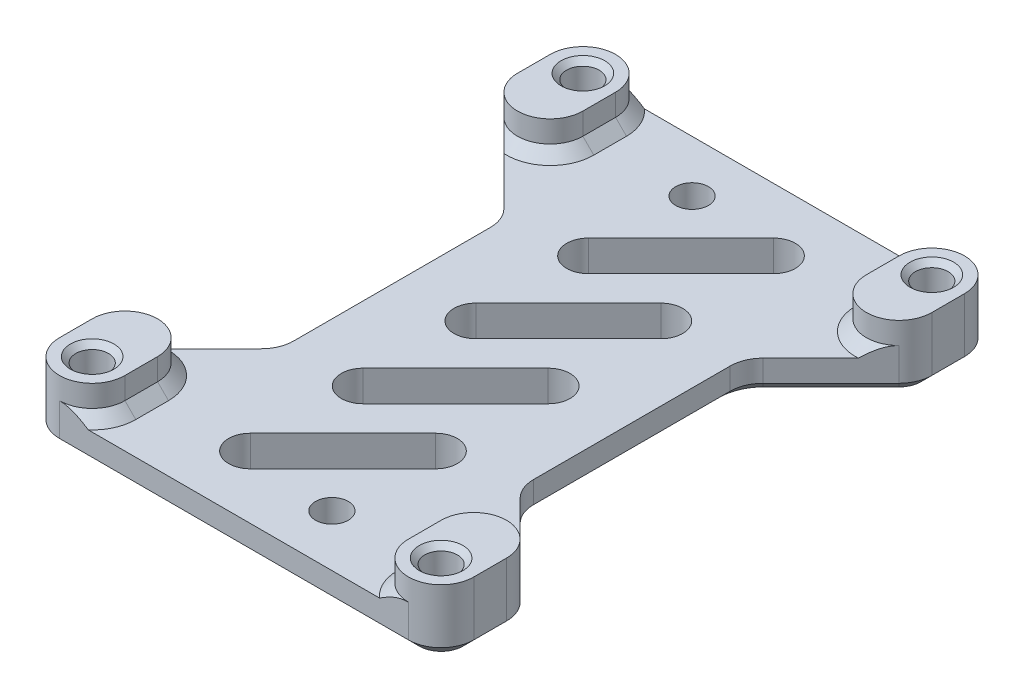
SolidWorks part; units mm, degrees
ref_plane "前视基准面" through (0, 0, 0) normal (0, 0, 1) x (1, 0, 0)
ref_plane "上视基准面" through (0, 0, 0) normal (0, 1, 0) x (1, 0, 0)
ref_plane "右视基准面" through (0, 0, 0) normal (1, 0, 0) x (0, 0, -1)
other "Configuration Table"
sketch "草图1" plane through (0, 0, 0) normal (0, 1, 0) x (1, 0, 0)
  line L1 (-19, -25.5) -> (19, -25.5)
  line L2 (-19, -25.5) -> (-19, 25.5)
  line L3 (-19, 25.5) -> (19, 25.5)
  line L4 (19, -25.5) -> (19, 25.5)
  line L5 (-19, -25.5) -> (19, 25.5) construction
  line L6 (-19, 25.5) -> (19, -25.5) construction
  point P0 (0, 0)
  dimension "D1" = 38
  dimension "D2" = 51
extrude "凸台-拉伸1" add sketch "草图1" along normal blind 6
sketch "草图2" plane through (0, 6, 0) normal (0, 1, 0) x (1, 0, 0)
  line L1 (-16, -22.5) -> (16, -22.5) construction
  line L2 (-16, -22.5) -> (-16, 22.5) construction
  line L3 (-16, 22.5) -> (16, 22.5) construction
  line L4 (16, -22.5) -> (16, 22.5) construction
  line L5 (-16, -22.5) -> (16, 22.5) construction
  line L6 (-16, 22.5) -> (16, -22.5) construction
  circle A0 centre (16, 22.5) radius 1.5
  circle A1 centre (16, -22.5) radius 1.5
  circle A2 centre (-16, 22.5) radius 1.5
  circle A3 centre (-16, -22.5) radius 1.5
  point P0 (0, 0)
  dimension "D3" = 3
  dimension "D1" = 45
  dimension "D2" = 32
extrude "切除-拉伸1" cut sketch "草图2" against normal blind 4
fillet "圆角1" radius 3 4 edges at (19, 3, 25.5) (-19, 3, 25.5) (-19, 3, -25.5) (19, 3, -25.5)
sketch "草图3" plane through (0, 6, 0) normal (0, 1, 0) x (1, 0, 0)
  line L0 (0, 0) -> (0, 25.5) construction
  line L1 (0, 25.5) -> (-16, 25.5) construction
  line L2 (-11, 9.0147) -> (-11, -9.0147)
  line L3 (-11, 0) -> (0, 0) construction
  line L4 (-16, -25.5) -> (16, -25.5)
  line L5 (19, -22.5) -> (19, 22.5)
  line L6 (16, 25.5) -> (-16, 25.5)
  line L7 (-19, 22.5) -> (-19, -22.5)
  line L8 (-16, -25.5) -> (16, -25.5) construction
  line L9 (19, -22.5) -> (19, -19.5) construction
  line L10 (16, 25.5) -> (0, 25.5) construction
  line L11 (-19, 22.5) -> (-19, 19.5) construction
  line L12 (-18.1213, 17.3787) -> (-11.8787, 11.136)
  line L13 (-18.1213, -17.3787) -> (-11.8787, -11.136)
  line L14 (18.1213, 17.3787) -> (11.8787, 11.136)
  line L15 (11, 9.0147) -> (11, -9.0147)
  line L16 (18.1213, -17.3787) -> (11.8787, -11.136)
  line L17 (-19, 19.5) -> (-19, -19.5)
  line L18 (-19, -19.5) -> (-19, -22.5) construction
  line L19 (19, -19.5) -> (19, 19.5)
  line L20 (19, 19.5) -> (19, 22.5) construction
  arc A0 (-11.8787, 11.136) -> (-11, 9.0147) centre (-14, 9.0147) cw
  arc A1 (-18.1213, 17.3787) -> (-19, 19.5) centre (-16, 19.5) cw
  arc A2 (-18.1213, -17.3787) -> (-19, -19.5) centre (-16, -19.5) ccw
  arc A3 (-11.8787, -11.136) -> (-11, -9.0147) centre (-14, -9.0147) ccw
  arc A4 (16, -25.5) -> (19, -22.5) centre (16, -22.5) ccw
  arc A5 (19, 22.5) -> (16, 25.5) centre (16, 22.5) ccw
  arc A6 (-16, 25.5) -> (-19, 22.5) centre (-16, 22.5) ccw
  arc A7 (-19, -22.5) -> (-16, -25.5) centre (-16, -22.5) ccw
  arc A8 (16, -25.5) -> (19, -22.5) centre (16, -22.5) ccw construction
  arc A9 (19, 22.5) -> (16, 25.5) centre (16, 22.5) ccw construction
  arc A10 (-16, 25.5) -> (-19, 22.5) centre (-16, 22.5) ccw construction
  arc A11 (-19, -22.5) -> (-16, -25.5) centre (-16, -22.5) ccw construction
  arc A12 (18.1213, 17.3787) -> (19, 19.5) centre (16, 19.5) ccw
  arc A13 (11.8787, 11.136) -> (11, 9.0147) centre (14, 9.0147) ccw
  arc A14 (11.8787, -11.136) -> (11, -9.0147) centre (14, -9.0147) cw
  arc A15 (18.1213, -17.3787) -> (19, -19.5) centre (16, -19.5) cw
  point P40 (0, 0)
  point P41 (-12.1815, 12.8178)
  dimension "D3" = 3
  dimension "D4" = 3
  dimension "D2" = 11
  dimension "D5" = 3
  dimension "D6" = 45
  dimension "D1" = 0
extrude "切除-拉伸2" cut sketch "草图3" against normal through all
chamfer "倒角1" distance 0.5 angle 45 4 edges at (16, 6, 24) (-16, 6, 24) (16, 6, -21) (-16, 6, -21)
sketch "草图4" plane through (0, 6, 0) normal (0, 1, 0) x (1, 0, 0)
  line L0 (0, 0) -> (0, 25.5) construction
  line L1 (-16, 16.5) -> (16, 16.5)
  line L2 (0, 0) -> (11, 0) construction
  line L3 (-16, -16.5) -> (16, -16.5)
  line L12 (-11.8787, -11.136) -> (-18.1213, -17.3787)
  line L13 (-19, -19.5) -> (-19, -22.5)
  line L14 (-16, -25.5) -> (16, -25.5)
  line L15 (19, -22.5) -> (19, -19.5)
  line L16 (18.1213, -17.3787) -> (11.8787, -11.136)
  line L17 (11, -9.0147) -> (11, 9.0147)
  line L18 (11.8787, 11.136) -> (18.1213, 17.3787)
  line L19 (19, 19.5) -> (19, 22.5)
  line L20 (16, 25.5) -> (-16, 25.5)
  line L21 (-19, 22.5) -> (-19, 19.5)
  line L22 (-18.1213, 17.3787) -> (-11.8787, 11.136)
  line L23 (-11, 9.0147) -> (-11, -9.0147)
  line L24 (-11.8787, -11.136) -> (-18.1213, -17.3787)
  line L25 (-19, -19.5) -> (-19, -22.5)
  line L26 (-16, -25.5) -> (16, -25.5)
  line L27 (19, -22.5) -> (19, -19.5)
  line L28 (18.1213, -17.3787) -> (11.8787, -11.136)
  line L29 (11, -9.0147) -> (11, 9.0147)
  line L30 (11.8787, 11.136) -> (18.1213, 17.3787)
  line L31 (19, 19.5) -> (19, 22.5)
  line L32 (16, 25.5) -> (-16, 25.5)
  line L33 (-19, 22.5) -> (-19, 19.5)
  line L34 (-18.1213, 17.3787) -> (-11.8787, 11.136)
  line L35 (-11, 9.0147) -> (-11, -9.0147)
  arc A0 (-18.1213, 17.3787) -> (-16, 16.5) centre (-16, 19.5) ccw
  arc A1 (18.1213, 17.3787) -> (16, 16.5) centre (16, 19.5) cw
  arc A2 (-18.1213, -17.3787) -> (-16, -16.5) centre (-16, -19.5) cw
  arc A3 (18.1213, -17.3787) -> (16, -16.5) centre (16, -19.5) ccw
  arc A12 (-18.1213, -17.3787) -> (-19, -19.5) centre (-16, -19.5) ccw
  arc A13 (-19, -22.5) -> (-16, -25.5) centre (-16, -22.5) ccw
  arc A14 (16, -25.5) -> (19, -22.5) centre (16, -22.5) ccw
  arc A15 (19, -19.5) -> (18.1213, -17.3787) centre (16, -19.5) ccw
  arc A16 (11, -9.0147) -> (11.8787, -11.136) centre (14, -9.0147) ccw
  arc A17 (11.8787, 11.136) -> (11, 9.0147) centre (14, 9.0147) ccw
  arc A18 (18.1213, 17.3787) -> (19, 19.5) centre (16, 19.5) ccw
  arc A19 (19, 22.5) -> (16, 25.5) centre (16, 22.5) ccw
  arc A20 (-16, 25.5) -> (-19, 22.5) centre (-16, 22.5) ccw
  arc A21 (-19, 19.5) -> (-18.1213, 17.3787) centre (-16, 19.5) ccw
  arc A22 (-11, 9.0147) -> (-11.8787, 11.136) centre (-14, 9.0147) ccw
  arc A23 (-11.8787, -11.136) -> (-11, -9.0147) centre (-14, -9.0147) ccw
  arc A24 (-18.1213, -17.3787) -> (-19, -19.5) centre (-16, -19.5) ccw
  arc A25 (-19, -22.5) -> (-16, -25.5) centre (-16, -22.5) ccw
  arc A26 (16, -25.5) -> (19, -22.5) centre (16, -22.5) ccw
  arc A27 (19, -19.5) -> (18.1213, -17.3787) centre (16, -19.5) ccw
  arc A28 (11, -9.0147) -> (11.8787, -11.136) centre (14, -9.0147) ccw
  arc A29 (11.8787, 11.136) -> (11, 9.0147) centre (14, 9.0147) ccw
  arc A30 (18.1213, 17.3787) -> (19, 19.5) centre (16, 19.5) ccw
  arc A31 (19, 22.5) -> (16, 25.5) centre (16, 22.5) ccw
  arc A32 (-16, 25.5) -> (-19, 22.5) centre (-16, 22.5) ccw
  arc A33 (-19, 19.5) -> (-18.1213, 17.3787) centre (-16, 19.5) ccw
  arc A34 (-11, 9.0147) -> (-11.8787, 11.136) centre (-14, 9.0147) ccw
  arc A35 (-11.8787, -11.136) -> (-11, -9.0147) centre (-14, -9.0147) ccw
  point P27 (0, 16.5)
  line M30 (-11.8787, -11.136) -> (-18.1213, -17.3787)
  line M38 (18.1213, -17.3787) -> (11.8787, -11.136)
  arc M39 (11.8787, -11.136) -> (11, -9.0147) centre (14, -9.0147) cw
  line M40 (11, -9.0147) -> (11, 9.0147)
  arc M41 (11, 9.0147) -> (11.8787, 11.136) centre (14, 9.0147) cw
  line M42 (11.8787, 11.136) -> (18.1213, 17.3787)
  line M50 (-18.1213, 17.3787) -> (-11.8787, 11.136)
  arc M51 (-11.8787, 11.136) -> (-11, 9.0147) centre (-14, 9.0147) cw
  line M52 (-11, 9.0147) -> (-11, -9.0147)
  arc M53 (-11, -9.0147) -> (-11.8787, -11.136) centre (-14, -9.0147) cw
  dimension "D1" = 0
extrude "切除-拉伸3" cut sketch "草图4" against normal blind 3 contours A3 A1 L1 A0 A2 L3 M38 M39 M40 M41 M42 M50 M51 M52 M53 M30 region at (0, 6, 0)
sketch "草图5" plane through (0, 6, 0) normal (0, 1, 0) x (1, 0, 0)
  line L0 (-16, 19.5) -> (16, 19.5) construction
  line L1 (-13, 22.5) -> (-13, 19.5)
  line L2 (0, 0) -> (0, 25.5) construction
  line L3 (0, 0) -> (19.4835, 0) construction
  line L4 (-16, 16.5) -> (16, 16.5)
  line L5 (19, 19.5) -> (19, 22.5)
  line L6 (16, 25.5) -> (-16, 25.5)
  line L7 (-19, 22.5) -> (-19, 19.5)
  line L8 (-16, 16.5) -> (16, 16.5)
  line L9 (19, 19.5) -> (19, 22.5) construction
  line L10 (16, 25.5) -> (-16, 25.5)
  line L11 (-19, 22.5) -> (-19, 19.5) construction
  line L13 (-13, -22.5) -> (-13, -19.5)
  line L14 (16, -25.5) -> (-16, -25.5)
  line L15 (13, -22.5) -> (13, -19.5)
  line L20 (13, 22.5) -> (13, 19.5)
  line L21 (-16, -16.5) -> (16, -16.5)
  arc A0 (-16, 16.5) -> (-13, 19.5) centre (-16, 19.5) ccw
  arc A1 (-16, 25.5) -> (-13, 22.5) centre (-16, 22.5) cw
  arc A2 (16, 25.5) -> (13, 22.5) centre (16, 22.5) ccw
  arc A3 (16, 16.5) -> (13, 19.5) centre (16, 19.5) cw
  arc A4 (-19, 19.5) -> (-16, 16.5) centre (-16, 19.5) ccw
  arc A5 (16, 16.5) -> (19, 19.5) centre (16, 19.5) ccw
  arc A6 (19, 22.5) -> (16, 25.5) centre (16, 22.5) ccw
  arc A7 (-16, 25.5) -> (-19, 22.5) centre (-16, 22.5) ccw
  arc A8 (-19, 19.5) -> (-16, 16.5) centre (-16, 19.5) ccw construction
  arc A9 (16, 16.5) -> (19, 19.5) centre (16, 19.5) ccw construction
  arc A10 (19, 22.5) -> (16, 25.5) centre (16, 22.5) ccw construction
  arc A11 (-16, 25.5) -> (-19, 22.5) centre (-16, 22.5) ccw construction
  arc A20 (-16, -16.5) -> (-13, -19.5) centre (-16, -19.5) cw
  arc A21 (-16, -25.5) -> (-13, -22.5) centre (-16, -22.5) ccw
  arc A22 (16, -25.5) -> (13, -22.5) centre (16, -22.5) cw
  arc A23 (16, -16.5) -> (13, -19.5) centre (16, -19.5) ccw
  point P16 (-23.8636, 15.0405)
  dimension "D1" = 0
extrude "切除-拉伸4" cut sketch "草图5" against normal blind 3
chamfer "倒角2" distance 1 angle 45 12 edges at (-13.8787, 3, -24.6213) (-14.8519, 3, -16.7284) (-13, 3, -21) (-14.8519, 3, 16.7284) (-13, 3, 21) (-13.8787, 3, 24.6213) (13.8787, 3, 24.6213) (14.8519, 3, 16.7284) (13, 3, 21) (13.8787, 3, -24.6213) (13, 3, -21) (14.8519, 3, -16.7284)
sketch "草图6" plane through (0, 3, 0) normal (0, 1, 0) x (1, 0, 0)
  line L0 (-4.2426, 11.2574) -> (4.2426, 19.7426) construction
  line L1 (-5.6569, 12.6716) -> (2.8284, 21.1569)
  line L2 (-2.8284, 9.8431) -> (5.6569, 18.3284)
  line L3 (0, 0) -> (0, 15.5) construction
  line L4 (-4.2426, 0.924) -> (4.2426, 9.4093) construction
  line L5 (-5.6569, 2.3382) -> (2.8284, 10.8235)
  line L6 (-2.8284, -0.4902) -> (5.6569, 7.9951)
  line L7 (-4.2426, -9.4093) -> (4.2426, -0.924) construction
  line L8 (-5.6569, -7.9951) -> (2.8284, 0.4902)
  line L9 (-2.8284, -10.8235) -> (5.6569, -2.3382)
  line L10 (-4.2426, -19.7426) -> (4.2426, -11.2574) construction
  line L11 (-5.6569, -18.3284) -> (2.8284, -9.8431)
  line L12 (-2.8284, -21.1569) -> (5.6569, -12.6716)
  line L13 (0, 5.1667) -> (0, -5.1667) construction
  line L14 (-13.3542, -25.5) -> (13.3542, -25.5) construction
  line L15 (-4.2426, 11.2574) -> (-4.2426, 20.7574) construction
  line L16 (4.2426, -20.7574) -> (4.2426, -11.2574) construction
  arc A0 (-5.6569, 12.6716) -> (-2.8284, 9.8431) centre (-4.2426, 11.2574) ccw
  arc A1 (5.6569, 18.3284) -> (2.8284, 21.1569) centre (4.2426, 19.7426) ccw
  arc A2 (-5.6569, 2.3382) -> (-2.8284, -0.4902) centre (-4.2426, 0.924) ccw
  arc A3 (5.6569, 7.9951) -> (2.8284, 10.8235) centre (4.2426, 9.4093) ccw
  arc A4 (-5.6569, -7.9951) -> (-2.8284, -10.8235) centre (-4.2426, -9.4093) ccw
  arc A5 (5.6569, -2.3382) -> (2.8284, 0.4902) centre (4.2426, -0.924) ccw
  arc A6 (-5.6569, -18.3284) -> (-2.8284, -21.1569) centre (-4.2426, -19.7426) ccw
  arc A7 (5.6569, -12.6716) -> (2.8284, -9.8431) centre (4.2426, -11.2574) ccw
  circle A8 centre (4.2426, -20.7574) radius 1.5
  circle A9 centre (-4.2426, 20.7574) radius 1.5
  point P2 (0, 15.5)
  point P14 (0, 5.1667)
  point P21 (0, -5.1667)
  point P28 (0, -15.5)
  dimension "D5" = 2
  dimension "D6" = 3
  dimension "D8" = 3
  dimension "D1" = 45
  dimension "D2" = 12
  dimension "D4" = 10
  dimension "D7" = 9.5
  dimension "D9" = 9.5
  dimension "D3" = 4
extrude "切除-拉伸5" cut sketch "草图6" against normal through all
chamfer "倒角3" distance 1 angle 45 24 edges at (-19, 0, -21) (-18.7716, 0, -18.3519) (-18.1213, 0, -24.6213) (-15, 0, -14.2574) (0, 0, -25.5) (-11.2284, 0, -10.1628) (18.1213, 0, -24.6213) (-11, 0, 0) (19, 0, -21) (-11.2284, 0, 10.1628) (18.7716, 0, -18.3519) (-15, 0, 14.2574) (15, 0, -14.2574) (-18.7716, 0, 18.3519) (11.2284, 0, -10.1628) (-19, 0, 21) (11, 0, 0) (-18.1213, 0, 24.6213) (11.2284, 0, 10.1628) (0, 0, 25.5) (15, 0, 14.2574) (18.1213, 0, 24.6213) (18.7716, 0, 18.3519) (19, 0, 21)
